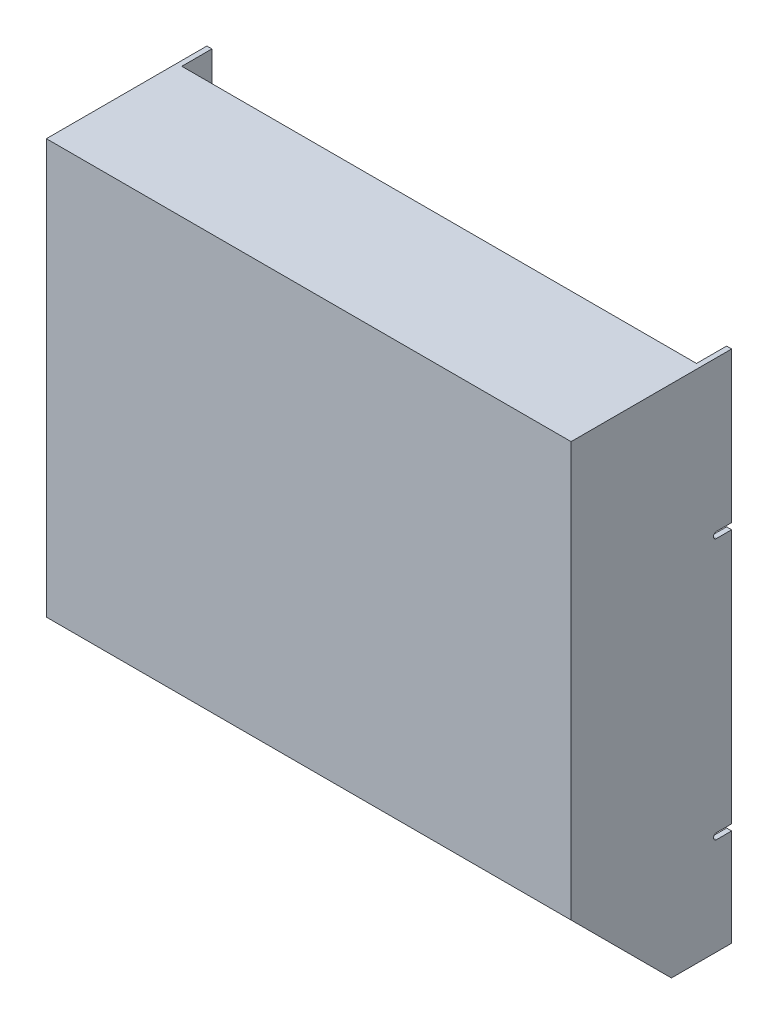
SolidWorks part; units mm, degrees
material "ABS PC generico"
ref_plane "Piano frontale" through (0, 0, 0) normal (0, 0, 1) x (1, 0, 0)
ref_plane "Piano superiore" through (0, 0, 0) normal (0, 1, 0) x (1, 0, 0)
ref_plane "Piano destro" through (0, 0, 0) normal (1, 0, 0) x (0, 0, -1)
sketch "Schizzo1" plane through (0, 0, 0) normal (0, 0, 1) x (1, 0, 0)
  line L0 (-200, -200) -> (-200, 200) construction
  line L1 (-230, -230) -> (230, -230) construction
  line L2 (-230, -230) -> (-230, 230) construction
  line L3 (-230, 230) -> (230, 230) construction
  line L4 (230, -230) -> (230, 230) construction
  line L5 (-230, -230) -> (230, 230) construction
  line L6 (-230, 230) -> (230, -230) construction
  line L7 (-200, 200) -> (200, 200) construction
  line L8 (200, -200) -> (200, 200) construction
  line L9 (-200, -200) -> (200, -200) construction
  point P0 (0, 0)
  dimension "D1" = 460
  dimension "D2" = 460
  dimension "D3" = 30
sketch "Schizzo2" plane through (0, 0, 0) normal (0, 0, 1) x (1, 0, 0)
  line L0 (-235, -230) -> (-235, 283)
  line L1 (288, -230) -> (-235, -230)
  line L2 (283, -225) -> (283, 278) construction
  line L3 (288, 283) -> (-235, 283)
  line L4 (-230, -225) -> (-230, 278) construction
  line L7 (288, -230) -> (288, 283)
  line L8 (283, 278) -> (-230, 278) construction
  line L9 (283, -225) -> (-230, -225) construction
  line L10 (283, -230) -> (-230, -230) construction
  line L11 (-230, -230) -> (-230, 283) construction
  line L12 (283, 283) -> (-230, 283) construction
  line L13 (283, -230) -> (283, 283) construction
  point P0 (0, 0)
  dimension "D1" = 523
  dimension "D2" = 513
  dimension "D3" = 5
  dimension "D4" = 5
  dimension "D5" = 5
  dimension "D6" = 5
extrude "Estrusione-Estrusione2" add sketch "Schizzo2" along normal blind 130
shell "Svuota1" thickness 5 removed face at (26.5, 26.5, 0)
sketch "Schizzo3" plane through (288, 0, 0) normal (1, 0, 0) x (0, 0, -1)
  line L0 (0, -311.6614) -> (0, 309.1506) construction
  line L1 (-30, -311.6614) -> (-30, 309.1506) construction
  line L2 (-130, -130) -> (-30, -230)
  line L3 (-130, -230) -> (-30, -230)
  line L4 (-130, -230) -> (-130, -130)
  line L5 (-130, -130) -> (-30, -130) construction
  line L6 (-30, -230) -> (-30, -130) construction
  line L7 (-130, -122.9289) -> (-22.9289, -230)
  line L8 (-30, -230) -> (-22.9289, -230)
  line L9 (-130, -130) -> (-130, -122.9289)
  line L11 (-126.4645, -126.4645) -> (-20.4648, -232.4641) construction
  line L14 (-130, -130) -> (-24.0003, -235.9997) construction
  line M3 (-130, 283) -> (-130, -230)
  line M4 (-130, -230) -> (0, -230)
  dimension "D2" = 100
  dimension "D3" = 100
  dimension "D5" = 7.0711
  dimension "D6" = 7.0711
  dimension "D1" = 30
  dimension "D4" = 5
extrude "Taglio-Estrusione2" cut sketch "Schizzo3" against normal up to surface (523 mm away) contours L2 M3 M4 region at (288, -196.6667, 96.6667) up to face at (-235, 26.5, 65)
extrude "Estrusione-Estrusione3" add sketch "Schizzo3<4>" against normal up to surface (523 mm away) contours L7 L2 M3 M4 region at (288, -178.2121, 78.2121) up to face at (-235, -4.8, 58)
sketch "Schizzo3<4>" plane through (288, 0, 0) normal (1, 0, 0) x (0, 0, -1) same geometry as "Schizzo3"
sketch "Schizzo5" plane through (0, 0, 0) normal (0, 0, 1) x (1, 0, 0)
  line L0 (283, -230) -> (288, -230)
  line L12 (16.5, 278) -> (16.5, 283)
  line L13 (-230, 278) -> (16.5, 278)
  line L14 (-230, -225) -> (-230, 278)
  line L15 (283, -225) -> (-230, -225)
  line L16 (283, 278) -> (283, -225)
  line L17 (36.5, 278) -> (283, 278)
  line L18 (36.5, 283) -> (36.5, 278)
  line L19 (288, 283) -> (36.5, 283)
  line L20 (288, -230) -> (288, 283)
  line L21 (-235, -230) -> (288, -230)
  line L22 (-235, 283) -> (-235, -230)
  line L23 (16.5, 283) -> (-235, 283)
  line L26 (-230, -230) -> (-230, 283)
  line L28 (283, 283) -> (283, -230)
  line L31 (288, 283) -> (283, 283)
  line L32 (288, -230) -> (288, 283)
  line L33 (-235, -230) -> (-230, -230)
  line L34 (-235, 283) -> (-235, -230)
  line L35 (-230, 283) -> (-235, 283)
  dimension "D1" = 0
extrude "Estrusione-Estrusione5" add sketch "Schizzo5" against normal blind 30
sketch "Schizzo6" plane through (-235, 0, 0) normal (-1, 0, 0) x (0, 0, 1)
  line L0 (0, 252.5489) -> (0, -248.8531) construction
  line L1 (-15, 252.5489) -> (-15, -248.8531) construction
  line L2 (-224.7552, 0) -> (0, 0) construction
  line L3 (-224.7552, -130) -> (0, -130) construction
  line L4 (-224.7552, 130) -> (0, 130) construction
  line L5 (-15, 133.05) -> (-30, 133.05)
  line L6 (-224.7552, 130) -> (336.9736, 130) construction
  line L7 (-224.7552, -130) -> (336.9736, -130) construction
  line L8 (-224.7552, 0) -> (336.9736, 0) construction
  line L9 (-15, 126.95) -> (-30, 126.95)
  line L10 (-30, 133.05) -> (-30, 126.95)
  line L12 (-30, -133.05) -> (-30, -126.95)
  line L13 (-15, -126.95) -> (-30, -126.95)
  line L14 (-15, -133.05) -> (-30, -133.05)
  arc A0 (-15, 126.95) -> (-15, 133.05) centre (-15, 130) ccw
  arc A1 (-15, -126.95) -> (-15, -133.05) centre (-15, -130) cw
  dimension "D4" = 3.05
  dimension "D1" = 15
  dimension "D2" = 130
  dimension "D3" = 130
extrude "Taglio-Estrusione4" cut sketch "Schizzo6" against normal up to surface (523 mm away) up to face at (288, -4.8, 46)
